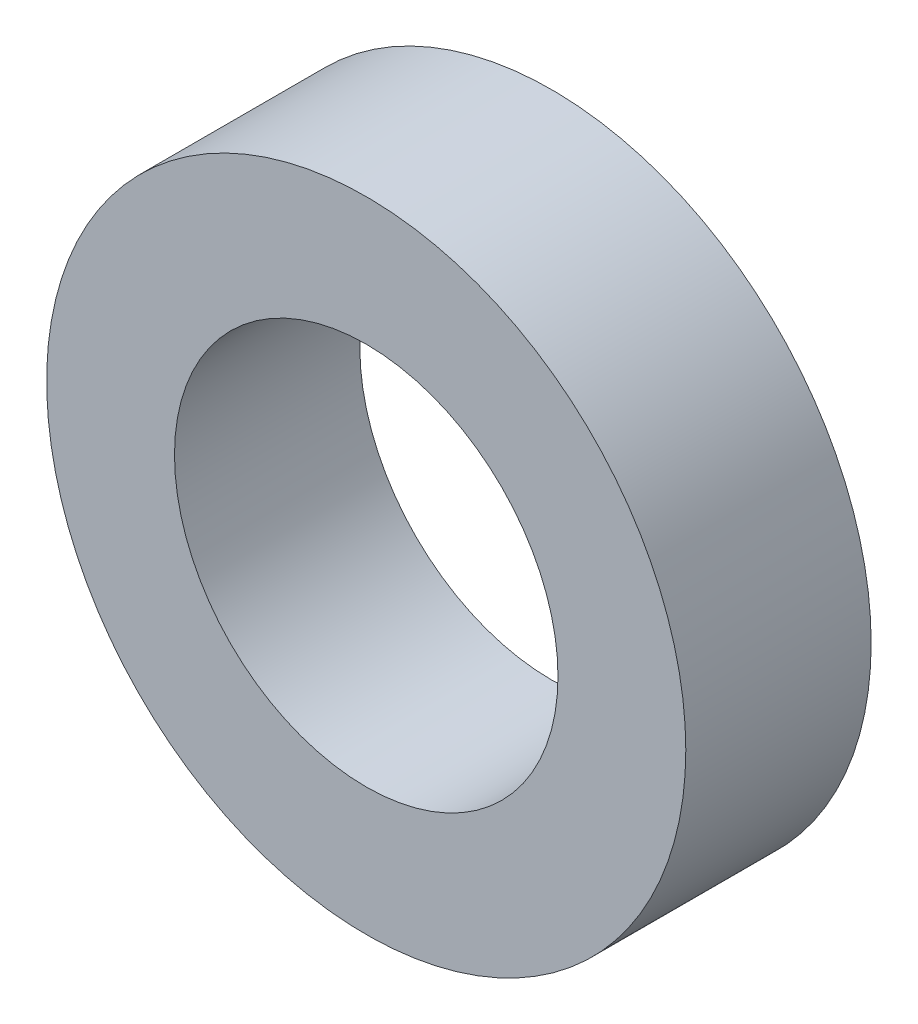
SolidWorks part; units mm, degrees
material "Acrylic (Medium-high impact)"
ref_plane "Front Plane" through (0, 0, 0) normal (0, 0, 1) x (1, 0, 0)
ref_plane "Top Plane" through (0, 0, 0) normal (0, 1, 0) x (1, 0, 0)
ref_plane "Right Plane" through (0, 0, 0) normal (1, 0, 0) x (0, 0, -1)
sketch "Sketch1" plane through (0, 0, 0) normal (0, 0, 1) x (1, 0, 0)
  circle A0 centre (0, 0) radius 3
  circle A1 centre (0, 0) radius 5
  dimension "D1" = 6
  dimension "D2" = 10
extrude "Boss-Extrude1" add sketch "Sketch1" along normal blind 2.9
equation "\"smallPulleyTeeth\"= 15"
equation "\"largePulleyTeeth\"= 30"
equation "\"eighthThick\"= 2.9mm"
equation "\"sixteenthThick\"= 1.7mm"
equation "\"quarterThick\"=6.0mm"
equation "\"OD\"= 145mm"
equation "\"puckAngle\"= 60.5deg"
equation "\"puckDiam\"= 76.5mm"
equation "\"axlePress\"= 5.9mm"
equation "\"press\"= 0.2mm"
equation "\"wheelClear\"= 0.3mm"
equation "\"10-32clear\"= 4.8mm"
equation "\"6-32clear\"= 3.3mm"
equation "\"8-32clear\"= 4.0mm"
equation "\"D1@Boss-Extrude1\"=\"eighthThick\""
